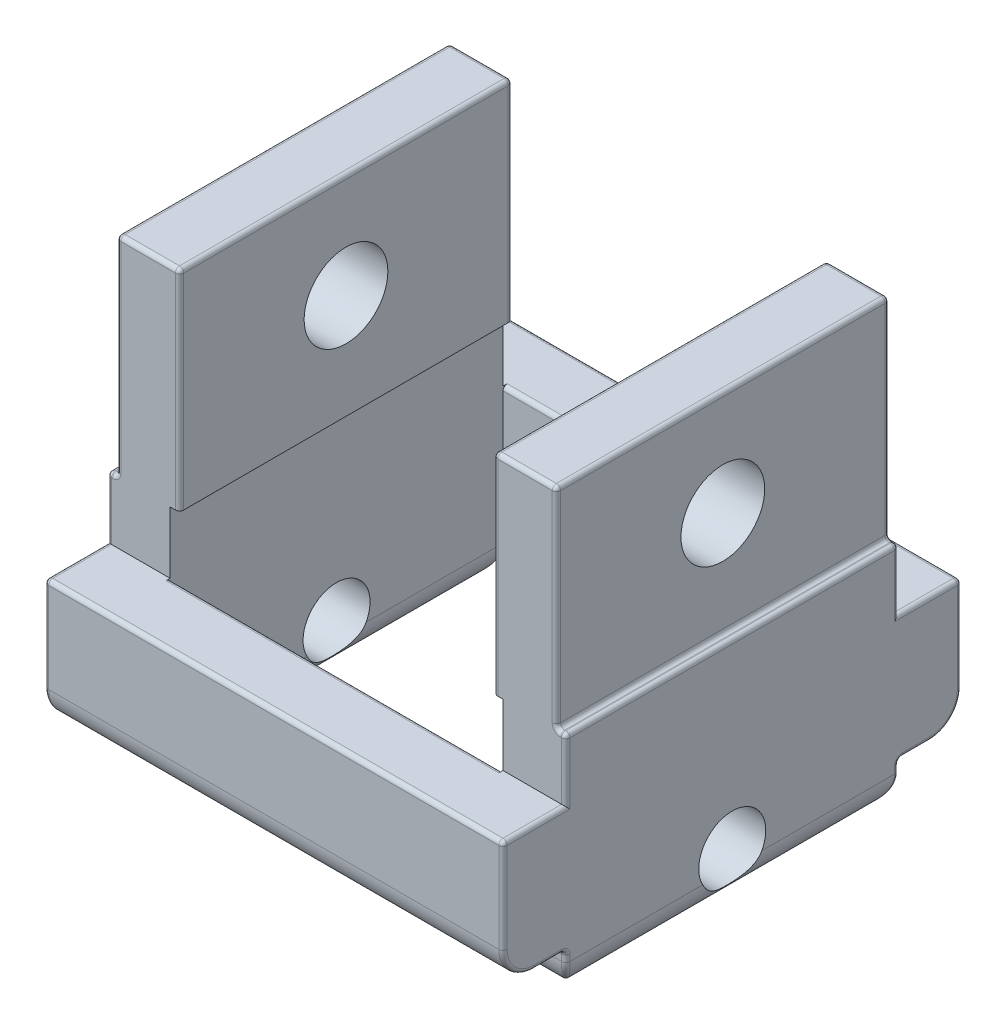
SolidWorks part; units mm, degrees
ref_plane "Front Plane" through (0, 0, 0) normal (0, 0, 1) x (1, 0, 0)
ref_plane "Top Plane" through (0, 0, 0) normal (0, 1, 0) x (1, 0, 0)
ref_plane "Right Plane" through (0, 0, 0) normal (1, 0, 0) x (0, 0, -1)
sketch "Sketch2" plane through (0, 0, 0) normal (0, 0, 1) x (1, 0, 0)
  line L0 (10.5, 5.4751) -> (10.9502, 5.4751)
  line L1 (-10.9502, -5.4751) -> (-7.9502, -5.4751)
  line L4 (-7.9502, -5.4751) -> (-7.9502, 5.4751)
  line L5 (-7.5, 5.4751) -> (-7.9502, 5.4751)
  line L6 (-10.9502, 5.4751) -> (-10.9502, -5.4751)
  line L7 (0, 30.75) -> (0, -21.7413) construction
  line L8 (0, -55) -> (0, 55) construction
  line L9 (7.5, 15.4751) -> (7.5, 5.4751)
  line L10 (10.5, 15.4751) -> (10.5, 5.4751)
  line L15 (-7.5, 15.4751) -> (-10.5, 15.4751)
  line L16 (-10.5, 15.4751) -> (-10.5, 5.4751)
  line L17 (7.5, 15.4751) -> (10.5, 15.4751)
  line L18 (-7.5, 15.4751) -> (-7.5, 5.4751)
  line L20 (10.9502, 5.4751) -> (10.9502, -5.4751)
  line L21 (7.5, 5.4751) -> (7.9502, 5.4751)
  line L22 (7.9502, -5.4751) -> (7.9502, 5.4751)
  line L23 (10.9502, -5.4751) -> (7.9502, -5.4751)
  line L24 (-10.5, 5.4751) -> (-10.9502, 5.4751)
  point P0 (-7.5, 4.175)
  point P5 (-10.9502, 0)
  point P25 (7.5, 4.175)
  dimension "D1" = 7.9502
  dimension "D2" = 3
  dimension "D3" = 10.9502
  dimension "D4" = 7.5
  dimension "D5" = 3
  dimension "D6" = 10
extrude "Boss-Extrude1" add sketch "Sketch2" along normal mid plane 15.9004
sketch "Sketch3" plane through (0, 0, 0) normal (1, 0, 0) x (0, 0, -1)
  line L0 (-7.9502, -5.4751) -> (7.9502, -5.4751) construction
  line L1 (-10.9502, -3.4751) -> (-7.9502, -3.4751)
  line L2 (-10.9502, -3.4751) -> (-10.9502, 2.5249)
  line L3 (-10.9502, 2.5249) -> (-7.9502, 2.5249)
  line L4 (-7.9502, -3.4751) -> (-7.9502, 2.5249)
  line L5 (-10.9502, -3.4751) -> (-7.9502, 2.5249) construction
  line L6 (-10.9502, 2.5249) -> (-7.9502, -3.4751) construction
  line L8 (0, 14.5393) -> (0, -15.5396) construction
  line L9 (10.9502, 2.5249) -> (7.9502, -3.4751) construction
  line L10 (10.9502, -3.4751) -> (7.9502, 2.5249) construction
  line L11 (7.9502, -3.4751) -> (7.9502, 2.5249)
  line L12 (10.9502, 2.5249) -> (7.9502, 2.5249)
  line L13 (10.9502, -3.4751) -> (10.9502, 2.5249)
  line L14 (10.9502, -3.4751) -> (7.9502, -3.4751)
  line L15 (-7.9502, -5.4751) -> (-7.9502, 5.4751) construction
  point P0 (-9.4502, -0.4751)
  point P16 (9.4502, -0.4751)
  dimension "D1" = 3
  dimension "D2" = 6
  dimension "D3" = 2
extrude "Boss-Extrude2" add sketch "Sketch3" along normal up to surface (10.9502 mm away) and the other way up to surface (10.9502 mm away) contours L2 L1 L4 L3 | L11 L12 L13 L14 up to face at (10.9502, 0, 0) other way up to face at (-10.9502, 0, 0)
sketch "Sketch4" plane through (10.5, 0, 0) normal (1, 0, 0) x (0, 0, -1)
  line L1 (-7.9502, 15.4751) -> (7.9502, 15.4751) construction
  circle A0 centre (0, 10.4751) radius 2
  dimension "D1" = 4
  dimension "D2" = 5
extrude "Cut-Extrude1" cut sketch "Sketch4" against normal through all both and the other way through all
sketch "Sketch5" plane through (10.9502, 0, 0) normal (1, 0, 0) x (0, 0, -1)
  line L1 (10.9502, -5.4751) -> (-10.9502, -5.4751) construction
  circle A0 centre (0, -3.2251) radius 1.6
  dimension "D1" = 3.2
  dimension "D2" = 2.25
extrude "Cut-Extrude2" cut sketch "Sketch5" against normal through all
ref_plane "Plane1" through (0, -3.2251, 0) normal (0, 1, 0) x (1, 0, 0)
fillet "Fillet1" radius 1.5 12 edges at (0, -3.4751, 7.9502) (-7.9502, -5.4751, 0) (0, -3.4751, 10.9502) (-10.9502, -5.4751, 0) (-9.4502, -5.4751, 7.9502) (-9.4502, -5.4751, -7.9502) (7.9502, -5.4751, 0) (9.4502, -5.4751, 7.9502) (10.9502, -5.4751, 0) (9.4502, -5.4751, -7.9502) (0, -3.4751, -7.9502) (0, -3.4751, -10.9502)
fillet "Fillet2" radius 0.2 55 edges at (-10.7251, 5.4751, 7.9502) (10.7251, 5.4751, 7.9502) (-10.7251, 5.4751, -7.9502) (10.7251, 5.4751, -7.9502) (10.5, 15.4751, 0) (9, 15.4751, 7.9502) (7.5, 15.4751, 0) (9, 15.4751, -7.9502) (-7.5, 15.4751, 0) (-9, 15.4751, 7.9502) (-10.5, 15.4751, 0) (-9, 15.4751, -7.9502) (0, 2.5249, 7.9502) (0, 2.5249, -7.9502) (-10.5, 10.4751, 7.9502) (10.5, 10.4751, 7.9502) (7.5, 10.4751, 7.9502) (-10.5, 10.4751, -7.9502) (-7.5, 10.4751, -7.9502) (-7.5, 10.4751, 7.9502) (7.5, 10.4751, -7.9502) (10.5, 10.4751, -7.9502) (10.9502, 0.2749, -10.9502) (10.9502, 0.2749, 10.9502) (-10.9502, 0.2749, 10.9502) (-10.5, 5.4751, 0) (10.5, 5.4751, 0) (10.9502, 5.4751, 0) (-10.9502, 5.4751, 0) (10.9502, -3.4751, -8.7002) (10.9502, -3.0358, -10.5109) (10.9502, -3.4751, 8.7002) (10.9502, -3.0358, 10.5109) (-10.9502, -3.4751, 8.7002) (-10.9502, -3.0358, 10.5109) (10.5109, -5.0358, -7.5109) (10.5109, -5.0358, 7.5109) (-10.5109, -5.0358, 7.5109) (10.9502, -3.7251, -7.9502) (10.9502, -3.7251, 7.9502) (-10.9502, -3.7251, 7.9502) (-9.4502, -3.4751, 7.9502) (9.4502, -3.4751, 7.9502) (9.4502, -3.4751, -7.9502) (-9.4502, -3.4751, -7.9502) (-10.9502, 4, 7.9502) (-10.9502, 2.5249, 9.4502) (10.9502, 2.5249, 9.4502) (10.9502, 4, 7.9502) (-10.9502, 4, -7.9502) (-10.9502, 2.5249, -9.4502) (10.9502, 4, -7.9502) (10.9502, 2.5249, -9.4502) (0, 2.5249, -10.9502) (0, 2.5249, 10.9502)
